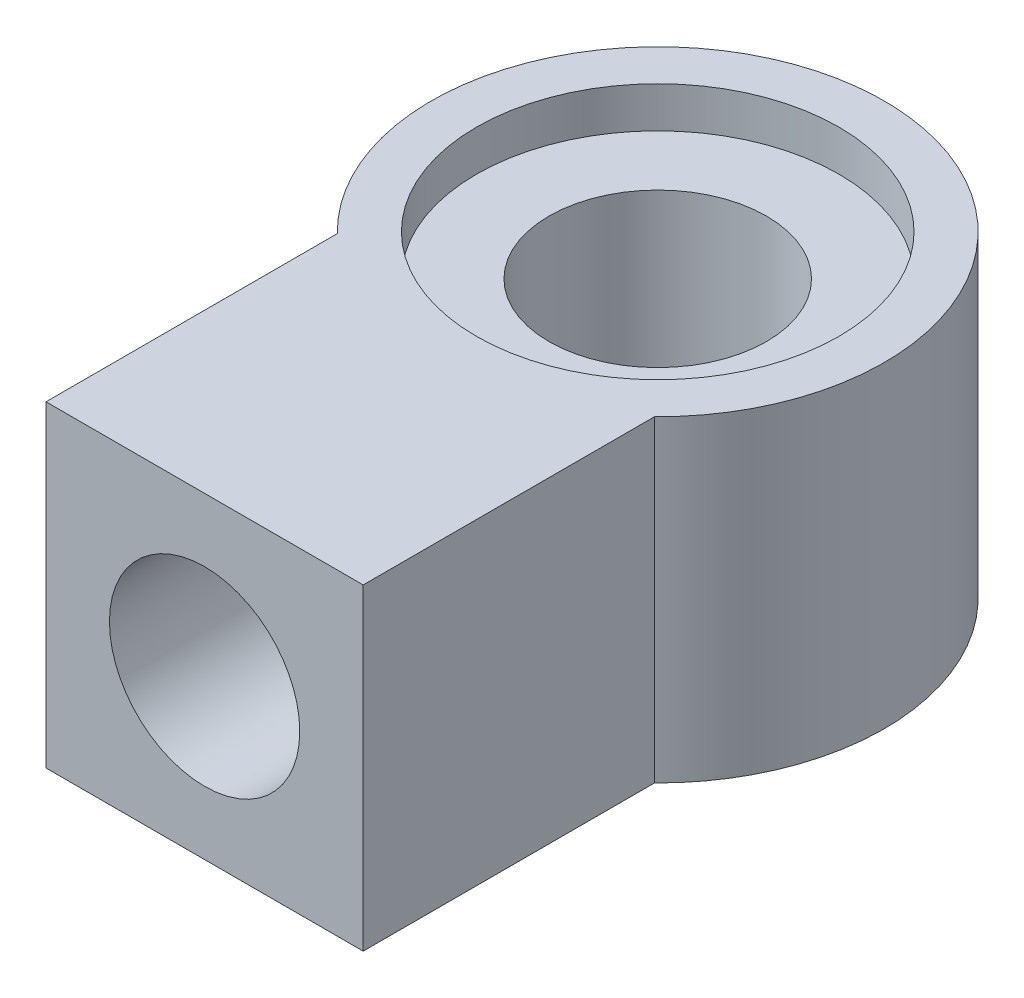
SolidWorks part; units mm, degrees
ref_plane "Front Plane" through (0, 0, 0) normal (0, 0, 1) x (1, 0, 0)
ref_plane "Top Plane" through (0, 0, 0) normal (0, 1, 0) x (1, 0, 0)
ref_plane "Right Plane" through (0, 0, 0) normal (1, 0, 0) x (0, 0, -1)
sketch "Sketch1" plane through (0, 0, 0) normal (0, 1, 0) x (1, 0, 0)
  circle A0 centre (0, 0) radius 5
  circle A1 centre (0, 0) radius 2.4
  dimension "D1" = 10
  dimension "D2" = 4.8
extrude "Boss-Extrude1" add sketch "Sketch1" along normal blind 7
ref_plane "Plane1" through (0, 0, 5) normal (0, 0, 1) x (1, 0, 0)
sketch "Sketch2" plane through (0, 0, 5) normal (0, 0, 1) x (1, 0, 0)
  line L0 (5, 7) -> (-5, 7) construction
  line L1 (3.5, 7) -> (-3.5, 7)
  line L2 (0, 7) -> (0, 0)
  line L3 (3.5, 0) -> (-3.5, 0)
  line L4 (-3.5, 7) -> (-3.5, 0)
  line L5 (-5, 0) -> (5, 0) construction
  line L6 (3.5, 7) -> (3.5, 0)
  dimension "D1" = 3.5
extrude "Boss-Extrude3" add sketch "Sketch2" against normal blind 1.5 contours L1 L4 L3 L2 | L6 L1 L2 L3 region at (1.75, 3.5, 5) region at (-1.75, 3.5, 5)
sketch "Sketch4" plane through (0, 0, 5) normal (0, 0, 1) x (1, 0, 0)
  line L1 (-3.5, 7) -> (3.5, 7)
  line L2 (-3.5, 7) -> (-3.5, 0)
  line L3 (-3.5, 0) -> (3.5, 0)
  line L4 (3.5, 7) -> (3.5, 0)
  circle A0 centre (0, 3.5) radius 2.1
  dimension "D1" = 4.2
extrude "Boss-Extrude4" add sketch "Sketch4" along normal blind 5
sketch "Sketch5" plane through (0, 7, 0) normal (0, 1, 0) x (1, 0, 0)
  circle A0 centre (0, 0) radius 4
  dimension "D1" = 8
extrude "Cut-Extrude1" cut sketch "Sketch5" against normal blind 0.9
